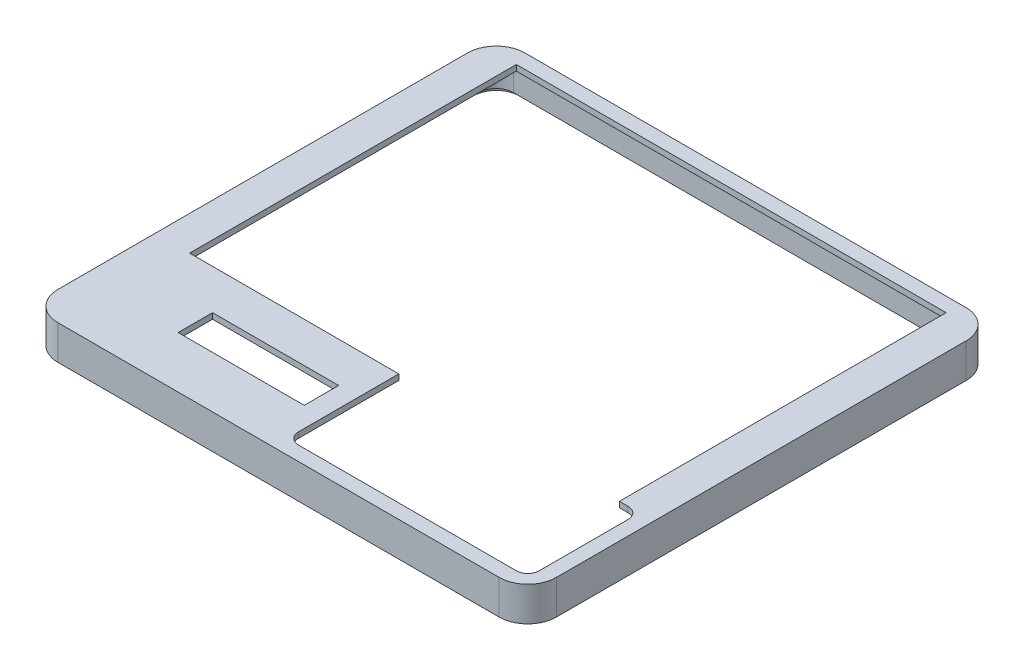
SolidWorks part; units mm, degrees
ref_plane "Спереди" through (0, 0, 0) normal (0, 0, 1) x (1, 0, 0)
ref_plane "Сверху" through (0, 0, 0) normal (0, 1, 0) x (1, 0, 0)
ref_plane "Справа" through (0, 0, 0) normal (1, 0, 0) x (0, 0, -1)
other "Configuration Table"
sketch "Эскиз1" plane through (0, 0, 0) normal (0, 1, 0) x (1, 0, 0)
  line L0 (41.4156, 1.5506) -> (41.4156, -75.9494)
  line L1 (2.9156, 1.5506) -> (79.9156, 1.5506) construction
  line L2 (-0.0844, -1.4494) -> (-0.0844, -72.9494) construction
  line L3 (2.9156, -75.9494) -> (79.9156, -75.9494) construction
  line L4 (82.9156, -1.4494) -> (82.9156, -72.9494) construction
  line L5 (-0.0844, -37.1994) -> (82.9156, -37.1994)
  line L6 (-2.0844, -1.4494) -> (-2.0844, -72.9494)
  line L7 (2.9156, -77.9494) -> (79.9156, -77.9494)
  line L8 (84.9156, -1.4494) -> (84.9156, -72.9494)
  line L9 (2.9156, 3.5506) -> (79.9156, 3.5506)
  line L10 (-0.0844, -1.4494) -> (-0.0844, -72.9494)
  line L11 (2.9156, -75.9494) -> (79.9156, -75.9494)
  line L12 (82.9156, -1.4494) -> (82.9156, -72.9494)
  line L13 (2.9156, 1.5506) -> (79.9156, 1.5506)
  circle A0 centre (9.9156, -65.9494) radius 3.9775
  circle A1 centre (9.9156, -8.4494) radius 3.9775
  circle A2 centre (72.9156, -8.4494) radius 3.9775
  circle A3 centre (72.9156, -65.9494) radius 3.9775
  arc A4 (79.9156, -75.9494) -> (82.9156, -72.9494) centre (79.9156, -72.9494) ccw construction
  arc A5 (79.9156, 1.5506) -> (82.9156, -1.4494) centre (79.9156, -1.4494) cw construction
  arc A6 (2.9156, 1.5506) -> (-0.0844, -1.4494) centre (2.9156, -1.4494) ccw construction
  arc A7 (-0.0844, -72.9494) -> (2.9156, -75.9494) centre (2.9156, -72.9494) ccw construction
  arc A8 (-2.0844, -72.9494) -> (2.9156, -77.9494) centre (2.9156, -72.9494) ccw
  arc A9 (79.9156, -77.9494) -> (84.9156, -72.9494) centre (79.9156, -72.9494) ccw
  arc A10 (79.9156, 3.5506) -> (84.9156, -1.4494) centre (79.9156, -1.4494) cw
  arc A11 (2.9156, 3.5506) -> (-2.0844, -1.4494) centre (2.9156, -1.4494) ccw
  arc A12 (-0.0844, -72.9494) -> (2.9156, -75.9494) centre (2.9156, -72.9494) ccw
  arc A13 (79.9156, -75.9494) -> (82.9156, -72.9494) centre (79.9156, -72.9494) ccw
  arc A14 (79.9156, 1.5506) -> (82.9156, -1.4494) centre (79.9156, -1.4494) cw
  arc A15 (2.9156, 1.5506) -> (-0.0844, -1.4494) centre (2.9156, -1.4494) ccw
  point P20 (82.9156, 1.5506)
  point P23 (-0.0844, 1.5506)
  point P26 (-0.0844, -75.9494)
  dimension "D3" = 10
  dimension "D5" = 3
  dimension "D1" = 83
  dimension "D2" = 77.5
  dimension "D4" = 10
extrude "Бобышка-Вытянуть4" add sketch "Эскиз1" along normal blind 1 contours L6 A8 L7 A9 L8 A10 L9 A11
sketch "Эскиз3" plane through (0, 0, 0) normal (0, -1, 0) x (1, 0, 0)
  line L12 (2.9156, -2.5506) -> (79.9156, -2.5506)
  line L13 (83.9156, 1.4494) -> (83.9156, 72.9494)
  line L14 (79.9156, 76.9494) -> (2.9156, 76.9494)
  line L15 (-1.0844, 72.9494) -> (-1.0844, 1.4494)
  line L16 (2.9156, -2.5506) -> (79.9156, -2.5506)
  line L17 (83.9156, 1.4494) -> (83.9156, 72.9494)
  line L18 (79.9156, 76.9494) -> (2.9156, 76.9494)
  line L19 (-1.0844, 72.9494) -> (-1.0844, 1.4494)
  arc A12 (-1.0844, 1.4494) -> (2.9156, -2.5506) centre (2.9156, 1.4494) ccw
  arc A13 (79.9156, -2.5506) -> (83.9156, 1.4494) centre (79.9156, 1.4494) ccw
  arc A14 (83.9156, 72.9494) -> (79.9156, 76.9494) centre (79.9156, 72.9494) ccw
  arc A15 (2.9156, 76.9494) -> (-1.0844, 72.9494) centre (2.9156, 72.9494) ccw
  arc A16 (-1.0844, 1.4494) -> (2.9156, -2.5506) centre (2.9156, 1.4494) ccw
  arc A17 (79.9156, -2.5506) -> (83.9156, 1.4494) centre (79.9156, 1.4494) ccw
  arc A18 (83.9156, 72.9494) -> (79.9156, 76.9494) centre (79.9156, 72.9494) ccw
  arc A19 (2.9156, 76.9494) -> (-1.0844, 72.9494) centre (2.9156, 72.9494) ccw
  dimension "D1" = 1
extrude "Бобышка-Вытянуть5" add sketch "Эскиз1<14>" against normal blind 5 contours L9 A11 L6 A8 L7 A9 L8 A10 A15 L13 A14 L12 A13 L11 A12 L10 region at (0.223, 0, -1.2431)
sketch "Эскиз1<14>" plane through (0, 0, 0) normal (0, 1, 0) x (1, 0, 0) same geometry as "Эскиз1"
extrude "Вырез-Вытянуть1" cut sketch "Эскиз3" against normal blind 1 from surface contours L19 A16 L16 A17 L17 A18 L18 A19 starting at face at (41.4156, -5, 37.1994)
sketch "Эскиз8" plane through (0, 0, 0) normal (0, -1, 0) x (1, 0, 0)
  line L5 (40.4156, 55.9494) -> (80.4156, 55.9494)
  line L6 (40.4156, 55.9494) -> (40.4156, 73.4494)
  line L7 (42.4156, 75.4494) -> (80.4156, 75.4494)
  line L8 (82.4156, 57.9494) -> (82.4156, 73.4494)
  line L9 (14.9156, 62.9494) -> (36.9156, 62.9494)
  line L10 (14.9156, 62.9494) -> (14.9156, 68.9494)
  line L11 (14.9156, 68.9494) -> (36.9156, 68.9494)
  line L12 (2.9156, -3.5506) -> (79.9156, -3.5506) construction
  line L13 (3.9156, -1.0506) -> (78.9156, -1.0506)
  line L14 (3.9156, -1.0506) -> (3.9156, 55.9494)
  line L15 (3.9156, 55.9494) -> (78.9156, 55.9494)
  line L16 (78.9156, -1.0506) -> (78.9156, 55.9494)
  line L17 (2.9156, 77.9494) -> (79.9156, 77.9494) construction
  line L18 (-2.0844, 1.4494) -> (-2.0844, 72.9494) construction
  line L19 (84.9156, 1.4494) -> (84.9156, 72.9494) construction
  line L20 (36.9156, 62.9494) -> (36.9156, 68.9494)
  arc A0 (80.4156, 75.4494) -> (82.4156, 73.4494) centre (80.4156, 73.4494) cw
  arc A1 (80.4156, 55.9494) -> (82.4156, 57.9494) centre (80.4156, 57.9494) ccw
  arc A2 (40.4156, 73.4494) -> (42.4156, 75.4494) centre (42.4156, 73.4494) cw
  point P25 (82.4156, 75.4494)
  point P31 (40.4156, 75.4494)
  dimension "D12" = 2
  dimension "D13" = 2
  dimension "D1" = 2.5
  dimension "D2" = 22
  dimension "D3" = 6
  dimension "D4" = 6
  dimension "D5" = 42
  dimension "D6" = 2.5
  dimension "D7" = 2.5
  dimension "D8" = 17
  dimension "D9" = 22
  dimension "D10" = 9
  dimension "D11" = 6
extrude "Вырез-Вытянуть2" cut sketch "Эскиз8" against normal through all both and the other way through all contours L14 L15 L16 L13 | L9 L20 L11 L10 | L6 A2 L7 A0 L8 A1 L5
sketch "Эскиз9" plane through (-2.0844, 0, 0) normal (-1, 0, 0) x (0, 0, 1)
  line L0 (77.9494, 1) -> (77.9494, -5) construction
  line L1 (59.9494, -2) -> (69.9494, -2)
  line L2 (59.9494, -2) -> (59.9494, -5)
  line L3 (59.9494, -5) -> (69.9494, -5)
  line L4 (69.9494, -2) -> (69.9494, -5)
  point P10 (69.4451, -1.2131)
  dimension "D1" = 10
  dimension "D2" = 8
  dimension "D4" = 3
extrude "Вырез-Вытянуть3" cut sketch "Эскиз9" against normal up to next
